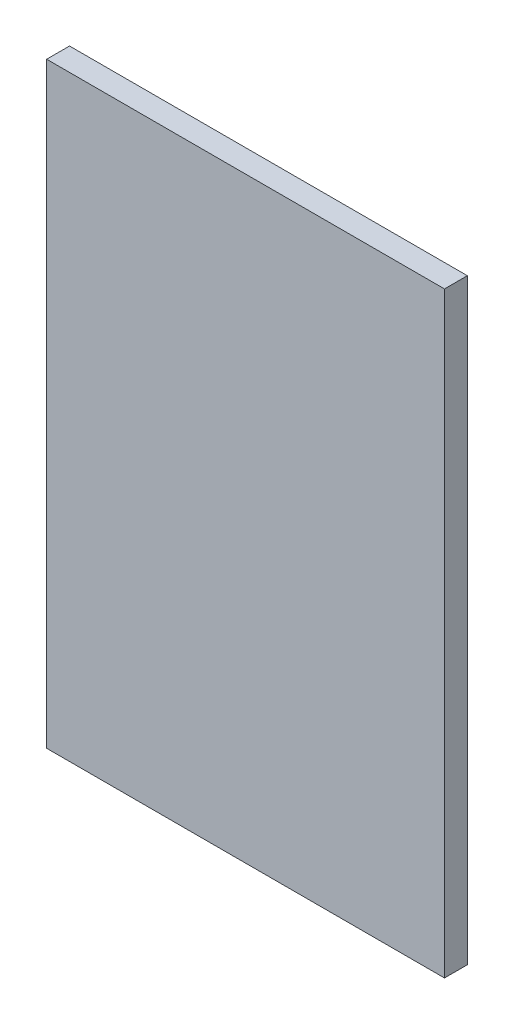
SolidWorks part; units mm, degrees
material "ABS PC"
ref_plane "Front Plane" through (0, 0, 0) normal (0, 0, 1) x (1, 0, 0)
ref_plane "Top Plane" through (0, 0, 0) normal (0, 1, 0) x (1, 0, 0)
ref_plane "Right Plane" through (0, 0, 0) normal (1, 0, 0) x (0, 0, -1)
sketch "Sketch1" plane through (0, 0, 0) normal (0, 0, 1) x (1, 0, 0)
  line L1 (0, 76.2) -> (50.8, 76.2)
  line L2 (0, 76.2) -> (0, 0)
  line L3 (0, 0) -> (50.8, 0)
  line L4 (50.8, 76.2) -> (50.8, 0)
  dimension "D1" = 50.8
  dimension "D2" = 76.2
extrude "Boss-Extrude1" add sketch "Sketch1" against normal blind 2.921
